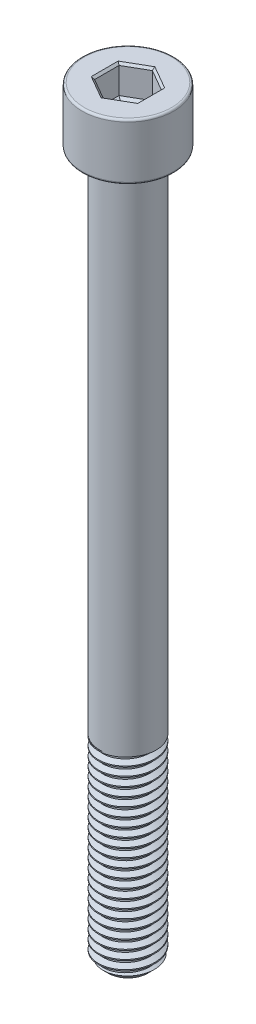
SolidWorks part; units mm, degrees
material "AISI Type A2 Tool Steel"
ref_plane "Front Plane" through (0, 0, 0) normal (0, 0, 1) x (1, 0, 0)
ref_plane "Top Plane" through (0, 0, 0) normal (0, 1, 0) x (1, 0, 0)
ref_plane "Right Plane" through (0, 0, 0) normal (1, 0, 0) x (0, 0, -1)
sketch "Sketch1" plane through (0, 0, 0) normal (0, 1, 0) x (1, 0, 0)
  circle A0 centre (0, 0) radius 4
  dimension "D1" = 8
extrude "Boss-Extrude1" add sketch "Sketch1" along normal blind 28
thread "Thread1" pitch 1.25 method cut profile "Thread Profile1" start angle 0, offset 2, length 0, pitch 1.25, diameter 8
ref_plane "Plane1" through (-4, 30, 0) normal (0, 0, 1) x (-1, 0, 0)
sketch "Thread Profile1" plane through (-4, 30, 0) normal (0, 0, 1) x (-1, 0, 0)
  line L0 (0, 0) -> (0, 1.25) construction
  line L11 (0, 0) -> (0, 1.0937)
  line L12 (0, 1.0937) -> (-0.6766, 0.7031)
  line L13 (-0.6766, 0.7031) -> (-0.6766, 0.3906)
  line L15 (-0.6766, 0.3906) -> (0, 0)
  line L17 (-0.6766, 0.5469) -> (0, 0.5469) construction
  point P2 (0, 0)
  dimension "Pitch" = 1.25
  dimension "Profile_Angle" = 60
  dimension "Profile_Land" = 0.3125
  dimension "Profile_Height" = 0.6766
sketch "Sketch2" plane through (0, 28, 0) normal (0, 1, 0) x (1, 0, 0)
  circle A0 centre (0, 0) radius 4
  dimension "D1" = 8
extrude "Boss-Extrude2" add sketch "Sketch2" along normal blind 72
sketch "Sketch5" plane through (0, 100, 0) normal (0, 1, 0) x (1, 0, 0)
  circle A0 centre (0, 0) radius 6.5
  dimension "D1" = 13
extrude "Boss-Extrude3" add sketch "Sketch5" along normal blind 8
sketch "Sketch6" plane through (0, 0, 0) normal (0, 0, 1) x (1, 0, 0)
  line L0 (0, 0) -> (0, 0.7245) construction
  line L1 (0, 0) -> (4.01, 0) construction
  line L2 (4.01, 0) -> (4.01, 1.2)
  line L3 (4.01, 1.2) -> (2.81, 0)
  line L4 (2.81, 0) -> (4.01, 0)
  dimension "D1" = 1.2
  dimension "D2" = 45
  dimension "D3" = 4.01
revolve "Cut-Revolve1" cut sketch "Sketch6" angle 360 about L0
fillet "Fillet1" radius 0.3 2 edges at (0, 100, 6.5) (0, 108, 6.5)
sketch "Sketch7" plane through (0, 108, 0) normal (0, 1, 0) x (1, 0, 0)
  line L1 (0, 3.4641) -> (-3, 1.7321)
  line L2 (-3, 1.7321) -> (-3, -1.7321)
  line L3 (-3, -1.7321) -> (0, -3.4641)
  line L4 (0, -3.4641) -> (3, -1.7321)
  line L5 (3, -1.7321) -> (3, 1.7321)
  line L6 (3, 1.7321) -> (0, 3.4641)
  circle A0 centre (0, 0) radius 3 construction
  dimension "D1" = 6
extrude "Cut-Extrude1" cut sketch "Sketch7" against normal blind 4
chamfer "Chamfer1" distance 0.3 angle 45 6 edges at (-3, 108, 0) (-1.5, 108, 2.5981) (1.5, 108, 2.5981) (3, 108, 0) (1.5, 108, -2.5981) (-1.5, 108, -2.5981)
sketch "Sketch8" plane through (0, 104, 0) normal (0, 1, 0) x (1, 0, 0)
  line L1 (0, 3.4641) -> (-3, 1.7321)
  line L2 (-3, 1.7321) -> (-3, -1.7321)
  line L3 (-3, -1.7321) -> (0, -3.4641)
  line L4 (0, -3.4641) -> (3, -1.7321)
  line L5 (3, -1.7321) -> (3, 1.7321)
  line L6 (3, 1.7321) -> (0, 3.4641)
  circle A0 centre (0, 0) radius 3 construction
extrude "Cut-Extrude2" cut sketch "Sketch8" against normal blind 0.4 draft 60
